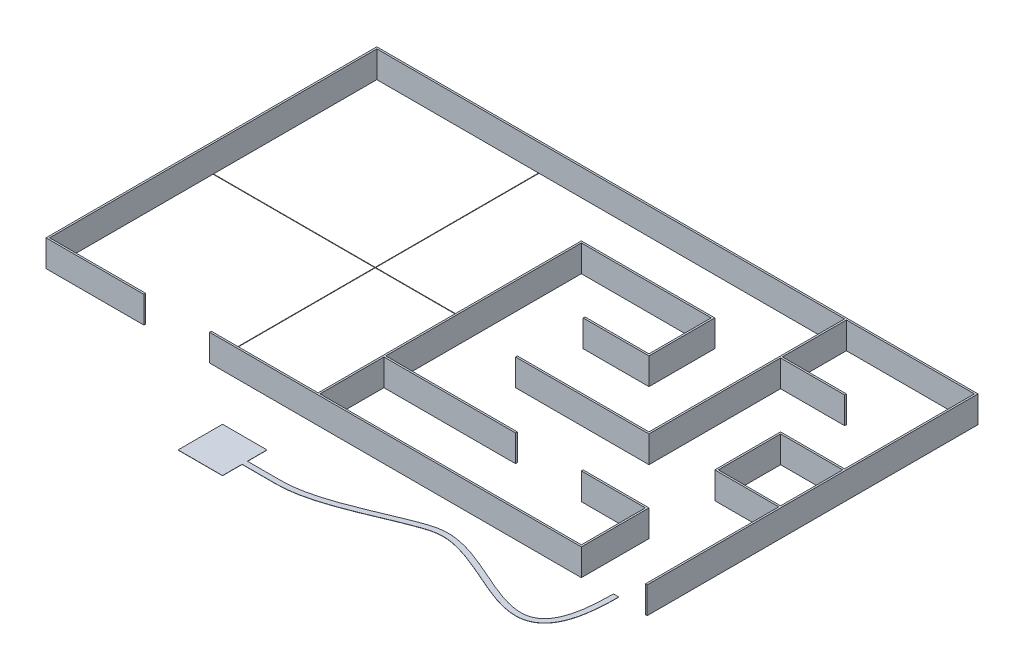
SolidWorks part; units mm, degrees
ref_plane "Front Plane" through (0, 0, 0) normal (0, 0, 1) x (1, 0, 0)
ref_plane "Top Plane" through (0, 0, 0) normal (0, 1, 0) x (1, 0, 0)
ref_plane "Right Plane" through (0, 0, 0) normal (1, 0, 0) x (0, 0, -1)
sketch "Sketch2" plane through (0, 0, 0) normal (0, 1, 0) x (1, 0, 0)
  line L0 (150, 757.4912) -> (150, 397.4912)
  line L5 (890, 767.4912) -> (140, 767.4912) construction
  line L6 (890, 757.4912) -> (140, 757.4912) construction
  line L7 (-2900, 2247.4912) -> (2000, 2247.4912) construction
  line L8 (-2900, 2247.4912) -> (-2900, -202.5088) construction
  line L9 (-2900, -202.5088) -> (2000, -202.5088) construction
  line L10 (2000, 2247.4912) -> (2000, -202.5088) construction
  line L11 (2000, 2247.4912) -> (140, 2247.4912) construction
  line L12 (2000, 2247.4912) -> (2000, 387.4912) construction
  line L13 (2000, 387.4912) -> (140, 387.4912) construction
  line L14 (140, 2247.4912) -> (140, 387.4912) construction
  line L15 (140, 2247.4912) -> (-1360, 2247.4912) construction
  line L16 (140, 2247.4912) -> (140, 387.4912) construction
  line L17 (140, 387.4912) -> (-1360, 387.4912) construction
  line L18 (-1360, 2247.4912) -> (-1360, 387.4912) construction
  line L24 (150, 1867.4912) -> (150, 397.4912) construction
  line L29 (0, 1877.4912) -> (2233.1632, 1877.4912) construction
  line L30 (0, 1507.4912) -> (2233.1632, 1507.4912) construction
  line L31 (0, 1137.4912) -> (2233.1632, 1137.4912) construction
  line L32 (0, 767.4912) -> (2233.1632, 767.4912) construction
  line L33 (520, 322.8834) -> (520, 2769.7829) construction
  line L34 (890, 322.8834) -> (890, 2730.1034) construction
  line L35 (1260, 322.8834) -> (1260, 2730.1034) construction
  line L36 (1630, 322.8834) -> (1630, 2730.1034) construction
  line L37 (2000, 387.4912) -> (2000, 2247.4912)
  line L38 (2000, 2247.4912) -> (140, 2247.4912)
  line L39 (140, 1877.4912) -> (140, 387.4912)
  line L40 (140, 387.4912) -> (1630, 387.4912)
  line L41 (1990, 1507.4912) -> (1630, 1507.4912)
  line L42 (1630, 1507.4912) -> (1630, 1137.4912)
  line L43 (1630, 1137.4912) -> (1990, 1137.4912)
  line L44 (1260, 2237.4912) -> (1260, 1137.4912)
  line L45 (1260, 1137.4912) -> (520, 1137.4912)
  line L46 (1270, 1877.4912) -> (1630, 1877.4912)
  line L47 (1260, 767.4912) -> (1630, 767.4912)
  line L48 (1630, 767.4912) -> (1630, 387.4912)
  line L49 (890, 767.4912) -> (150, 767.4912)
  line L50 (140, 1877.4912) -> (890, 1877.4912)
  line L51 (890, 1877.4912) -> (890, 1507.4912)
  line L52 (890, 1507.4912) -> (520, 1507.4912)
  line L53 (1260, 757.4912) -> (1620, 757.4912)
  line L54 (1620, 757.4912) -> (1620, 397.4912)
  line L55 (150, 397.4912) -> (1620, 397.4912)
  line L56 (150, 1867.4912) -> (150, 767.4912)
  line L57 (150, 1867.4912) -> (880, 1867.4912)
  line L58 (880, 1867.4912) -> (880, 1517.4912)
  line L59 (880, 1517.4912) -> (520, 1517.4912)
  line L60 (890, 757.4912) -> (150, 757.4912)
  line L61 (1990, 387.4912) -> (1990, 1137.4912)
  line L62 (1990, 2237.4912) -> (1270, 2237.4912)
  line L63 (1270, 2237.4912) -> (1270, 1877.4912)
  line L64 (1270, 1127.4912) -> (520, 1127.4912)
  line L65 (1270, 1867.4912) -> (1630, 1867.4912)
  line L66 (1990, 1497.4912) -> (1640, 1497.4912)
  line L67 (1640, 1497.4912) -> (1640, 1147.4912)
  line L68 (1640, 1147.4912) -> (1990, 1147.4912)
  line L69 (140, 2237.4912) -> (140, 2247.4912)
  line L70 (520, 1517.4912) -> (520, 1507.4912)
  line L71 (520, 1137.4912) -> (520, 1127.4912)
  line L72 (890, 757.4912) -> (890, 767.4912)
  line L73 (1260, 767.4912) -> (1260, 757.4912)
  line L74 (1630, 1877.4912) -> (1630, 1867.4912)
  line L75 (1990, 387.4912) -> (2000, 387.4912)
  line L76 (1260, 2237.4912) -> (140, 2237.4912)
  line L77 (1260, 1877.4912) -> (1630, 1877.4912) construction
  line L78 (1260, 1867.4912) -> (1630, 1867.4912) construction
  line L79 (1270, 2247.4912) -> (1270, 1127.4912) construction
  line L80 (1260, 2247.4912) -> (1260, 1137.4912) construction
  line L81 (1270, 1867.4912) -> (1270, 1127.4912)
  line L82 (1990, 2237.4912) -> (140, 2237.4912) construction
  line L83 (1990, 1507.4912) -> (1990, 2237.4912)
  line L84 (2000, 1507.4912) -> (1630, 1507.4912) construction
  line L85 (2000, 1497.4912) -> (1640, 1497.4912) construction
  line L86 (1990, 1147.4912) -> (1990, 1497.4912)
  line L87 (1990, 387.4912) -> (1990, 2237.4912) construction
  line L88 (1630, 1137.4912) -> (2000, 1137.4912) construction
  line L89 (1640, 1147.4912) -> (2000, 1147.4912) construction
  dimension "D3" = 4900
  dimension "D4" = 2450
  dimension "D6" = 1860
  dimension "D8" = 1500
  dimension "D11" = 370
  dimension "D12" = 370
  dimension "D13" = 370
  dimension "D14" = 370
  dimension "D15" = 370
  dimension "D16" = 370
  dimension "D17" = 370
  dimension "D18" = 370
  dimension "D20" = 10
  dimension "D21" = 10
  dimension "D22" = 10
  dimension "D23" = 10
  dimension "D24" = 10
sketch "Sketch3" plane through (0, 0, 0) normal (0, 1, 0) x (1, 0, 0)
  line L0 (-125, -125) -> (125, -125)
  line L1 (-125, -125) -> (-125, 125)
  line L2 (-125, 125) -> (125, 125)
  line L3 (125, -125) -> (125, -15)
  line L4 (125, -15) -> (315.8408, -15)
  line L5 (1830, 387.4912) -> (1830, 397.7572)
  line L6 (125, 15) -> (315.8408, 15)
  line L7 (1800, 387.4912) -> (1800, 397.7572)
  line L8 (1800, 397.7572) -> (1830, 397.7572)
  line L9 (125, 15) -> (125, 125)
  line L10 (-125, 125) -> (125, -125) construction
  line L11 (125, 125) -> (-125, -125) construction
  spline S0 degree 3 poles (315.8408, -15) (320.3892, -15) (329.4726, -14.8763) (347.7358, -14.1516) (370.663, -12.3833) (398.3223, -8.9846) (435.3465, -2.8859) (481.8254, 7.4249) (537.6725, 23.3117) (593.3447, 41.9419) (648.5876, 62.5542) (703.1388, 84.3925) (756.728, 106.7031) (809.0751, 128.7341) (851.4242, 146.2332) (884.3823, 159.3424) (908.6156, 168.6324) (932.2627, 177.3002) (955.2977, 184.9736) (978.0248, 191.3219) (1000.6899, 196.0306) (1019.77, 198.345) (1035.3212, 199.0724) (1051.2205, 199.0504) (1071.675, 197.6768) (1105.5397, 192.8242) (1149.7407, 182.2259) (1204.9561, 163.8148) (1261.5713, 141.3706) (1318.87, 116.5871) (1376.1824, 91.1706) (1432.8813, 66.8305) (1488.387, 45.2802) (1542.1831, 28.2504) (1593.8412, 17.5308) (1643.0145, 15.0761) (1689.2437, 23.1954) (1731.1957, 44.4017) (1760.7336, 74.0854) (1780.5549, 105.2195) (1793.5177, 132.3812) (1804.5689, 163.5188) (1813.7021, 198.8399) (1819.6948, 231.9502) (1823.4982, 260.762) (1825.8489, 283.5623) (1827.6911, 307.5838) (1828.7963, 328.6435) (1829.4186, 346.1319) (1829.7533, 359.5698) (1829.9213, 371.047) (1829.9887, 380.3804) (1830, 385.1276) (1830, 387.4912) knots 0 0 0 0 0.007812 0.015625 0.03125 0.046875 0.0625 0.09375 0.125 0.15625 0.1875 0.21875 0.25 0.28125 0.3125 0.328125 0.34375 0.359375 0.375 0.390625 0.40625 0.421875 0.429688 0.4375 0.453125 0.46875 0.5 0.53125 0.5625 0.59375 0.625 0.65625 0.6875 0.71875 0.75 0.78125 0.8125 0.84375 0.875 0.890625 0.90625 0.921875 0.9375 0.953125 0.960938 0.96875 0.976562 0.984375 0.988281 0.992188 0.996094 0.998047 1 1 1 1
  spline S1 degree 3 poles (315.8408, 15) (320.1225, 15) (328.6642, 15.1163) (345.9124, 15.8002) (367.6525, 17.4756) (394.029, 20.7151) (429.5184, 26.5591) (474.3908, 36.5065) (528.7407, 51.9619) (583.2848, 70.211) (637.7208, 90.5198) (691.7542, 112.1493) (745.0988, 134.3574) (797.4773, 156.4017) (840.0979, 174.014) (873.4507, 187.2806) (898.0626, 196.716) (922.246, 205.5826) (946.4193, 213.6422) (970.8297, 220.4696) (995.7449, 225.6565) (1017.1139, 228.2566) (1034.6734, 229.0773) (1052.4063, 229.0499) (1074.9013, 227.5314) (1111.4909, 222.2766) (1158.2086, 211.0421) (1215.3822, 191.9601) (1273.1662, 169.0438) (1331.001, 144.025) (1388.2804, 118.6234) (1444.3557, 94.5552) (1498.5305, 73.5329) (1550.0453, 57.2519) (1598.0524, 47.3468) (1641.6228, 45.2942) (1673.5536, 51.0415) (1696.4999, 60.6073) (1712.5329, 70.4822) (1727.4867, 83.3652) (1741.3899, 99.632) (1754.1716, 119.6531) (1765.6959, 143.747) (1775.8051, 172.1751) (1784.3476, 205.1586) (1790.0476, 236.608) (1793.6966, 264.2415) (1795.9641, 286.2275) (1797.7494, 309.4984) (1798.8247, 329.9812) (1799.4316, 347.0347) (1799.7585, 360.1591) (1799.923, 371.3853) (1799.989, 380.5232) (1800, 385.1755) (1800, 387.4912) knots 0 0 0 0 0.007812 0.015625 0.03125 0.046875 0.0625 0.09375 0.125 0.15625 0.1875 0.21875 0.25 0.28125 0.3125 0.328125 0.34375 0.359375 0.375 0.390625 0.40625 0.421875 0.429688 0.4375 0.453125 0.46875 0.5 0.53125 0.5625 0.59375 0.625 0.65625 0.6875 0.71875 0.75 0.78125 0.8125 0.828125 0.84375 0.859375 0.875 0.890625 0.90625 0.921875 0.9375 0.953125 0.960938 0.96875 0.976562 0.984375 0.988281 0.992188 0.996094 0.998047 1 1 1 1
  point P12 (0, 0)
extrude "Boss-Extrude3" add sketch "Sketch2" along normal blind 150 contours L56 L49 L72 L60 L0 L55 L54 L53 L73 L47 L48 L40 L39 L50 L51 L52 L70 L59 L58 L57 | L61 L43 L42 L41 L83 L62 L63 L46 L74 L65 L81 L64 L71 L45 L44 L76 L69 L38 L37 L75 | L66 L67 L68 L86
extrude "Boss-Extrude4" add sketch "Sketch3" along normal blind 1 separate body
sketch "Sketch4" plane through (0, 0, 0) normal (0, 1, 0) x (1, 0, 0)
  line L0 (140, 387.4912) -> (1630, 387.4912) construction
  line L1 (140, 2247.4912) -> (-1380, 2247.4912)
  line L2 (140, 2247.4912) -> (140, 2237.4912)
  line L3 (140, 387.4912) -> (-460, 387.4912)
  line L4 (-1380, 2247.4912) -> (-1380, 387.4912)
  line L7 (-1370, 2237.4912) -> (-1370, 397.4912)
  line L8 (130, 2237.4912) -> (-1370, 2237.4912)
  line L9 (130, 2237.4912) -> (140, 2237.4912)
  line L11 (140, 1877.4912) -> (140, 387.4912)
  line L12 (-460, 397.4912) -> (140, 397.4912)
  line L13 (140, 2247.4912) -> (140, 387.4912) construction
  line L14 (130, 2237.4912) -> (130, 397.4912) construction
  line L15 (-1754.9483, 1317.4912) -> (402.192, 1317.4912) construction
  line L16 (-460, 2502.5502) -> (-460, 94.0506) construction
  line L17 (-460, 397.4912) -> (-460, 387.4912)
  line L18 (-830, 397.4912) -> (-830, 387.4912)
  line L19 (-830, 397.4912) -> (-1370, 397.4912)
  line L20 (-830, 387.4912) -> (-1380, 387.4912)
  line L21 (130, 397.4912) -> (-1370, 397.4912) construction
  line L23 (140, 387.4912) -> (-1380, 387.4912) construction
  line L24 (-460, 387.4912) -> (140, 387.4912)
  line L25 (-460, 387.4912) -> (-460, 397.4912)
  line L26 (-460, 397.4912) -> (140, 397.4912)
  line L27 (140, 387.4912) -> (140, 397.4912)
  dimension "D1" = 1520
  dimension "D3" = 600
  dimension "D4" = 920
  dimension "D5" = 370
  dimension "D2" = 10
extrude "Boss-Extrude5" add sketch "Sketch4" along normal blind 150 contours L12 L17 L3 L11 | L4 L20 L18 L19 L7 L8 L9 L2 L1 region at (-160, 0, -392.4912)
sketch "Sketch5" plane through (0, 0, 0) normal (0, 1, 0) x (1, 0, 0)
  line L0 (-460, 397.4912) -> (-460, 2237.4912) construction
  line L1 (-1370, 1317.4912) -> (140, 1317.4912) construction
  line L2 (1260, 2237.4912) -> (-1370, 2237.4912) construction
  line L3 (140, 1877.4912) -> (140, 397.4912) construction
  line L5 (-1370, 1316.4912) -> (140, 1316.4912)
  line L6 (-1370, 1318.4912) -> (140, 1318.4912)
  line L7 (-1370, 1318.4912) -> (-1370, 1316.4912)
  line L8 (140, 1318.4912) -> (140, 1316.4912)
  line L9 (-460, 397.4912) -> (140, 397.4912) construction
  line L10 (-458, 397.4912) -> (-458, 2237.4912)
  line L11 (-460, 397.4912) -> (-460, 2237.4912)
  line L12 (-460, 2237.4912) -> (-458, 2237.4912)
  line L13 (-460, 397.4912) -> (-458, 397.4912)
  dimension "D1" = 920
  dimension "D2" = 600
  dimension "D3" = 1
  dimension "D4" = 1
  dimension "D5" = 2
  dimension "D6" = 2
extrude "Boss-Extrude6" add sketch "Sketch5" along normal blind 1 contours L5 L11 L6 L7 | L11 L13 L10 L5 | L11 L5 L10 L6 | L10 L5 L8 L6 | L12 L11 L6 L10 region at (-915, 0, -1317.4912) region at (-459, 0, -1317.4912) region at (-459, 0, -856.9912) region at (-159, 0, -1317.4912) region at (-459, 0, -1777.9912)
